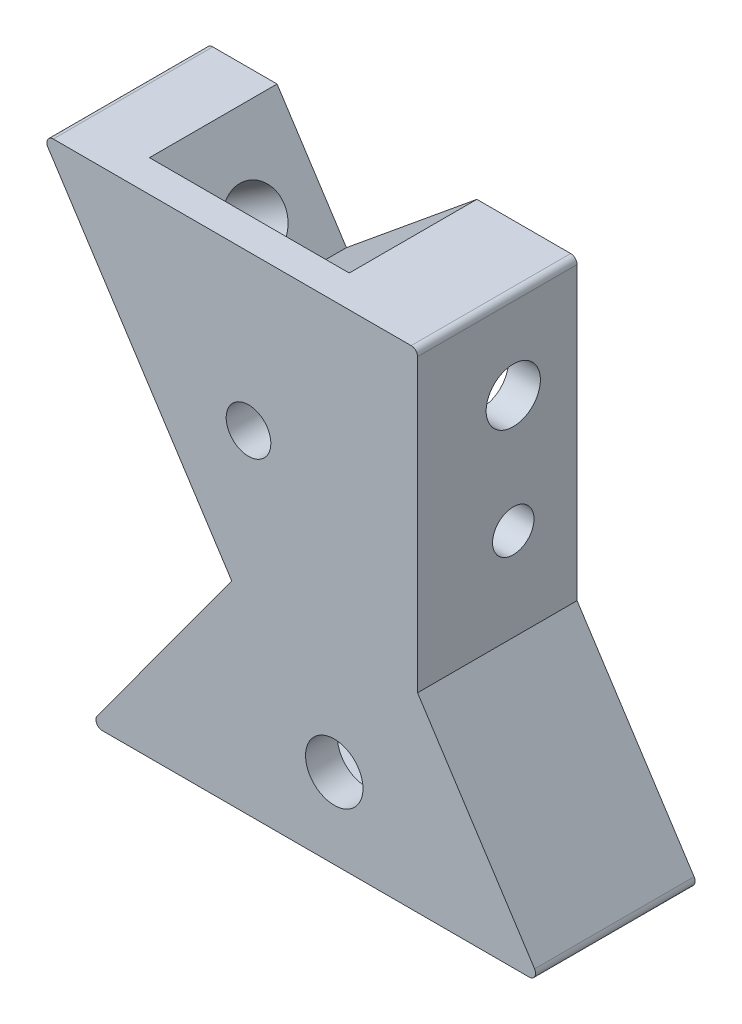
SolidWorks part; units mm, degrees
material "ABS"
ref_plane "Спереди" through (0, 0, 0) normal (0, 0, 1) x (1, 0, 0)
ref_plane "Сверху" through (0, 0, 0) normal (0, 1, 0) x (1, 0, 0)
ref_plane "Справа" through (0, 0, 0) normal (1, 0, 0) x (0, 0, -1)
sketch "Sketch1" plane through (0, 0, 0) normal (0, 0, 1) x (1, 0, 0)
  line L0 (0, 0) -> (70.7083, 0)
  line L1 (70.7083, 0) -> (51.3681, 29.8437)
  line L2 (51.3681, 29.8437) -> (51.3681, 76.4582)
  line L3 (51.3681, 76.4582) -> (-7.5636, 76.4582)
  line L4 (-7.5636, 76.4582) -> (22.2451, 30.4604)
  line L5 (22.2451, 30.4604) -> (0, 0)
extrude "Boss-Extrude1" add sketch "Sketch1" against normal blind 25
fillet "Fillet1" radius 1 4 edges at (-7.5636, 76.4582, -12.5) (51.3681, 76.4582, -12.5) (70.7083, 0, -12.5) (0, 0, -12.5)
sketch "Sketch3" plane through (0, 0, 0) normal (0, 0, 1) x (1, 0, 0)
  circle A0 centre (24.8766, 52.1885) radius 3.5
  circle A1 centre (38.3141, 12.5485) radius 4.5
  dimension "D1" = 7
  dimension "D2" = 9
extrude "Cut-Extrude1" cut sketch "Sketch3" against normal through all
sketch "Sketch5" plane through (51.3681, 0, 0) normal (1, 0, 0) x (0, 0, -1)
  line L0 (0, 29.8437) -> (0, 75.4582) construction
  circle A0 centre (15, 44.3231) radius 3.25
  circle A1 centre (15, 62.7091) radius 4.25
  dimension "D1" = 6.5
  dimension "D2" = 8.5
  dimension "D3" = 15
  dimension "D4" = 15
extrude "Cut-Extrude2" cut sketch "Sketch5" against normal blind 15
sketch "Sketch6" plane through (29.5676, 19.1612, 0) normal (-0.8392, -0.5438, 0) x (0, 0, 1)
  line L0 (0, 66.4367) -> (0, 13.4644) construction
  circle A0 centre (-15, 49.6524) radius 4.5
  dimension "D1" = 9
  dimension "D2" = 15
extrude "Cut-Extrude3" cut sketch "Sketch6" against normal through all
sketch "Sketch7" plane through (0, 0, -25) normal (0, 0, -1) x (-1, 0, 0)
  line L0 (-46.3681, 71.4582) -> (-46.3681, 32.9604)
  line L1 (-46.3681, 32.9604) -> (-26.5831, 32.9604)
  line L2 (-26.5831, 32.9604) -> (-14.0696, 52.27)
  line L3 (-37.4505, 71.4582) -> (-46.3681, 71.4582)
  line L4 (-46.6305, 27.9604) -> (-61.5099, 5)
  line L5 (-61.5099, 5) -> (-9.8429, 5)
  line L6 (-9.8429, 5) -> (-26.6108, 27.9604)
  line L7 (-26.6108, 27.9604) -> (-46.6305, 27.9604)
  line L8 (-69.7078, 1.5438) -> (-51.3681, 29.8437) construction
  line L9 (-1.9686, 0) -> (-68.8686, 0) construction
  line L10 (-22.2451, 30.4604) -> (-1.161, 1.5898) construction
  line L11 (6.5631, 74.9143) -> (-22.2451, 30.4604) construction
  line L12 (-51.3681, 29.8437) -> (-51.3681, 75.4582) construction
  line L13 (-50.3681, 76.4582) -> (5.7239, 76.4582) construction
  line L14 (-37.4505, 71.4582) -> (-14.0696, 52.27)
  line L15 (-35.6615, 76.4582) -> (-15.2227, 59.6846)
  line L16 (-15.2227, 59.6846) -> (-4.3526, 76.4582)
  line L17 (-35.6615, 76.4582) -> (-4.3526, 76.4582)
  dimension "D1" = 5
  dimension "D2" = 5
  dimension "D3" = 5
  dimension "D4" = 5
  dimension "D5" = 5
  dimension "D6" = 5
  dimension "D7" = 5
  dimension "D8" = 2.5
  dimension "D9" = 5
  dimension "D10" = 10
extrude "Cut-Extrude4" cut sketch "Sketch7" against normal blind 20
sketch "Sketch8" plane through (0, 0, 0) normal (0, -1, 0) x (1, 0, 0)
  circle A0 centre (17.5726, -13.1827) radius 7.5
  circle A1 centre (56.4379, -13.1827) radius 7.5
  dimension "D1" = 15
extrude "Boss-Extrude2" add sketch "Sketch8" along normal blind 2.5
